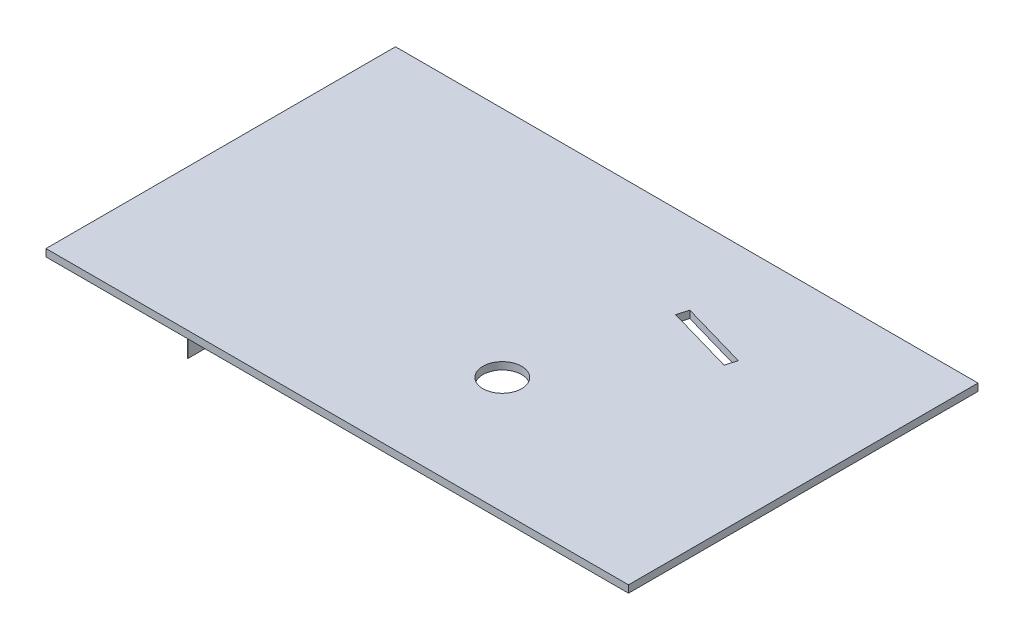
SolidWorks part; units mm, degrees
material "Particle Board"
ref_plane "Front Plane" through (0, 0, 0) normal (0, 0, 1) x (1, 0, 0)
ref_plane "Top Plane" through (0, 0, 0) normal (0, 1, 0) x (1, 0, 0)
ref_plane "Right Plane" through (0, 0, 0) normal (1, 0, 0) x (0, 0, -1)
sketch "Sketch3" plane through (0, 0, 0) normal (0, 1, 0) x (1, 0, 0)
  line L1 (0, 0) -> (-839.8654, 0) construction
  line L2 (0, 0) -> (-451.1992, 260.5) construction
  line L5 (-524, 0) -> (-525.5875, 0)
  line L6 (277.6777, 444.3772) -> (277.6777, 446.248)
  circle A0 centre (0, 0) radius 254 construction
  arc A3 (277.6777, 444.3772) -> (-524, 0) centre (0, 0) ccw
  arc A4 (277.6777, 446.248) -> (-525.5875, 0) centre (0, 0) ccw
  arc A5 (278.5189, 445.7235) -> (-525.5875, 0) centre (0, 0) ccw construction
  dimension "D1" = 524
  dimension "D2" = 1.5875
  dimension "D4" = 122
  dimension "D5" = 508
  dimension "D3" = 30
extrude "Boss-Extrude1" add sketch "Sketch3" along normal blind 50.8
sketch "Sketch4" plane through (0, 50.8, 0) normal (0, 1, 0) x (1, 0, 0)
  line L5 (-889, 609.6) -> (635, 609.6)
  line L6 (-889, 609.6) -> (-889, -304.8)
  line L7 (-889, -304.8) -> (635, -304.8)
  line L8 (635, 609.6) -> (635, -304.8)
  dimension "D1" = 304.8
  dimension "D2" = 1524
  dimension "D3" = 914.4
  dimension "D4" = 635
extrude "Boss-Extrude2" add sketch "Sketch4" along normal blind 19.05
hole_wizard "Ø20.0mm Dowel Hole1" positions "Sketch6" profile "Sketch7" hole size "Ø20.0" standard "ANSI Metric" end condition through all
sketch "Sketch6" plane through (0, 50.8, 0) normal (0, -1, 0) x (-1, 0, 0)
  point P0 (0, 0)
sketch "Sketch7" plane through (0, 50.8, 0) normal (1, 0, 0) x (0, 0, -1)
  line L0 (0, 0) -> (0, 19.05)
  line L1 (0, 19.05) -> (50.8, 19.05)
  line L2 (50.8, 19.05) -> (50.8, 0)
  line L5 (50.8, 0) -> (0, 0)
  line L11 (0, -6.35) -> (0, 107.95) construction
  dimension "Thru Hole Dia." = 101.6
  dimension "Thru Hole Depth" = 19.05
ref_plane "Plane1" through (0, 0, 298.45) normal (0, 0, 1) x (1, 0, 0)
sketch "Sketch8" plane through (0, 0, 0) normal (0, 0, 1) x (1, 0, 0)
  line L0 (-524, 50.8) -> (-524, 0) construction
  line L1 (-525.5875, 50.8) -> (-524, 50.8)
  line L2 (-525.5875, 50.8) -> (-525.5875, 0)
  line L3 (-525.5875, 0) -> (-524, 0)
  line L4 (-524, 50.8) -> (-524, 0)
  line L5 (-525.5875, 50.8) -> (-525.5875, 0) construction
  line L6 (-525.5875, 0) -> (-524, 0) construction
  line L7 (-525.5875, 50.8) -> (-524, 50.8) construction
extrude "Boss-Extrude3" add sketch "Sketch8" along normal up to surface (298.45 mm away) up to plane "Plane1"
sketch "Sketch9" plane through (0, 50.8, 0) normal (0, -1, 0) x (-1, 0, 0)
  line L0 (-92.8177, 397.8388) -> (-270.6511, 346.8459)
  line L1 (-270.6511, 346.8459) -> (-262.382, 318.008)
  line L2 (-262.382, 318.008) -> (-84.5486, 369.0009)
  line L3 (-84.5486, 369.0009) -> (-92.8177, 397.8388)
  line L6 (0, 0) -> (-635, 0) construction
  line L7 (-635, -304.8) -> (-635, 609.6) construction
  dimension "D1" = 185
  dimension "D2" = 30
  dimension "D3" = 16
  dimension "D4" = 262.382
  dimension "D5" = 318.008
extrude "Cut-Extrude1" cut sketch "Sketch9" against normal through all
sketch "Sketch10" plane through (0, 69.85, 0) normal (0, -1, 0) x (-1, 0, 0)
  line L0 (0, 0) -> (-545.6, 0) construction
  line L1 (0, 0) -> (277.6777, 444.3772) construction
  line L2 (0, 0) -> (195.5256, 509.3615) construction
  line L3 (0, 0) -> (94.7424, 537.3111) construction
  circle A0 centre (0, 0) radius 545.6 construction
  dimension "D1" = 11
  dimension "D2" = 11
